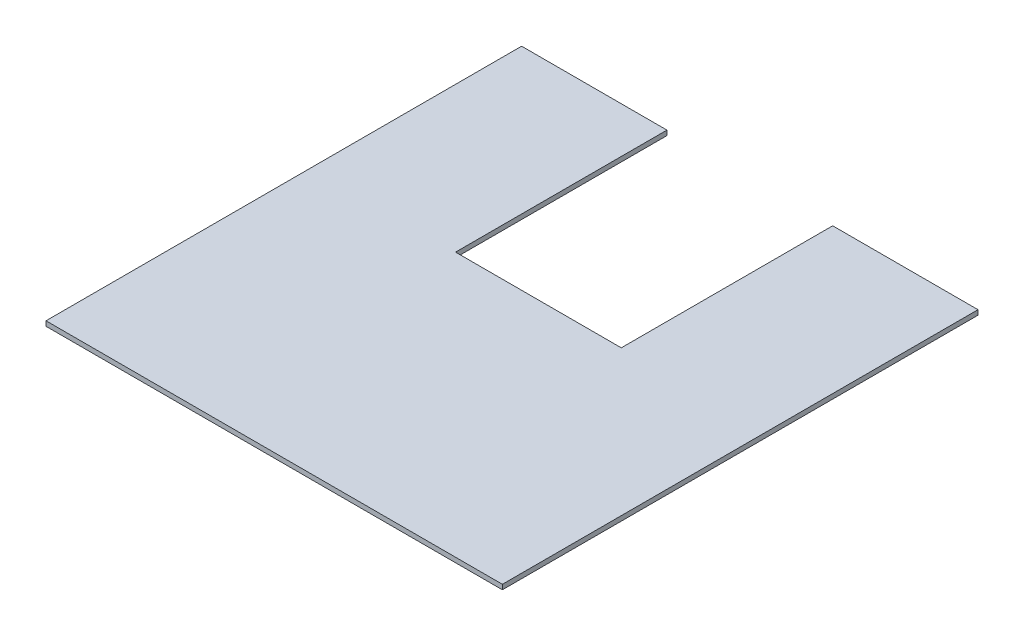
SolidWorks part; units mm, degrees
ref_plane "Front Plane" through (0, 0, 0) normal (0, 0, 1) x (1, 0, 0)
ref_plane "Top Plane" through (0, 0, 0) normal (0, 1, 0) x (1, 0, 0)
ref_plane "Right Plane" through (0, 0, 0) normal (1, 0, 0) x (0, 0, -1)
sketch "Sketch1" plane through (0, 0, 0) normal (0, 1, 0) x (1, 0, 0)
  line L1 (-95, -99) -> (95, -99)
  line L2 (-95, -99) -> (-95, 99)
  line L3 (-95, 99) -> (95, 99)
  line L4 (95, -99) -> (95, 99)
  line L5 (-95, -99) -> (95, 99) construction
  line L6 (-95, 99) -> (95, -99) construction
  point P0 (0, 0)
  dimension "D1" = 190
  dimension "D2" = 198
extrude "Boss-Extrude1" add sketch "Sketch1" along normal mid plane 2
sketch "Sketch2" plane through (0, 1, 0) normal (0, 1, 0) x (1, 0, 0)
  line L0 (95, 99) -> (-95, 99) construction
  line L1 (-34.5, 11) -> (34.5, 11)
  line L2 (-34.5, 11) -> (-34.5, 99)
  line L3 (-34.5, 99) -> (34.5, 99)
  line L4 (34.5, 11) -> (34.5, 99)
  line L5 (-34.5, 11) -> (34.5, 99) construction
  line L6 (-34.5, 99) -> (34.5, 11) construction
  point P0 (0, 55)
  point P7 (0, 0)
  dimension "D1" = 69
  dimension "D2" = 88
extrude "Cut-Extrude1" cut sketch "Sketch2" against normal through all
